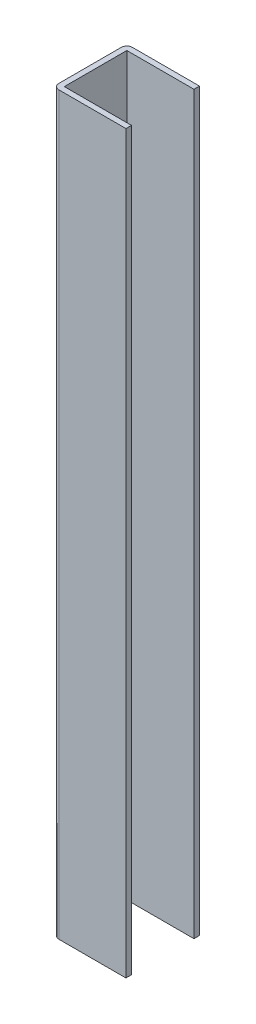
SolidWorks part; units mm, degrees
ref_plane "Спереди" through (0, 0, 0) normal (0, 0, 1) x (1, 0, 0)
ref_plane "Сверху" through (0, 0, 0) normal (0, 1, 0) x (1, 0, 0)
ref_plane "Справа" through (0, 0, 0) normal (1, 0, 0) x (0, 0, -1)
sketch "Эскиз1" plane through (0, 0, 0) normal (0, 1, 0) x (1, 0, 0)
  line L1 (-37, 20) -> (37, 20)
  line L2 (-40, 17) -> (-40, -17)
  line L3 (-37, -20) -> (37, -20)
  line L4 (40, 17) -> (40, -17)
  line L5 (-40, 20) -> (40, -20) construction
  line L6 (-40, -20) -> (40, 20) construction
  arc A0 (-37, 20) -> (-40, 17) centre (-37, 17) ccw
  arc A1 (-40, -17) -> (-37, -20) centre (-37, -17) ccw
  arc A2 (37, -20) -> (40, -17) centre (37, -17) ccw
  arc A3 (37, 20) -> (40, 17) centre (37, 17) cw
  point P0 (0, 0)
  dimension "D1" = 3
extrude "Вытянуть-Тонкостенный1" add sketch "Эскиз1" along normal blind 400 thin thin type one direction reverse wall 3
sketch "Эскиз2" plane through (0, 400, 0) normal (0, 1, 0) x (1, 0, 0)
  line L1 (-0.5, -21.5541) -> (41.1465, -21.5541)
  line L2 (-0.5, -21.5541) -> (-0.5, 20.9728)
  line L3 (-0.5, 20.9728) -> (41.1465, 20.9728)
  line L4 (41.1465, -21.5541) -> (41.1465, 20.9728)
extrude "Вырез-Вытянуть1" cut sketch "Эскиз2" against normal through all
